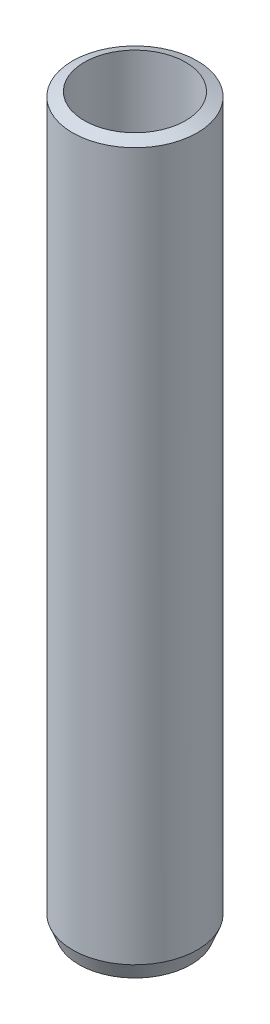
SolidWorks part; units mm, degrees
ref_plane "Front Plane" through (0, 0, 0) normal (0, 0, 1) x (1, 0, 0)
ref_plane "Top Plane" through (0, 0, 0) normal (0, 1, 0) x (1, 0, 0)
ref_plane "Right Plane" through (0, 0, 0) normal (1, 0, 0) x (0, 0, -1)
sketch "Sketch1" plane through (0, 0, 0) normal (0, 1, 0) x (1, 0, 0)
  circle A0 centre (0, 0) radius 32.5
  dimension "SHAFT_OD" = 65
extrude "Boss-Extrude1" add sketch "Sketch1" along normal blind 380.4451
sketch "Sketch2" plane through (0, 0, 0) normal (0, 1, 0) x (1, 0, 0)
  circle A0 centre (0, 0) radius 26.3875
  dimension "BORE_D" = 52.7751
extrude "Cut-Extrude1" cut sketch "Sketch2" along normal through all
chamfer "Chamfer1" distance 3.3059 angle 68.279 2 edges at (0, 380.4451, 32.5) (0, 0, 32.5) first distance on face at (0, 380.4451, 32.5) first distance on face at (0, 0, 26.3875)
